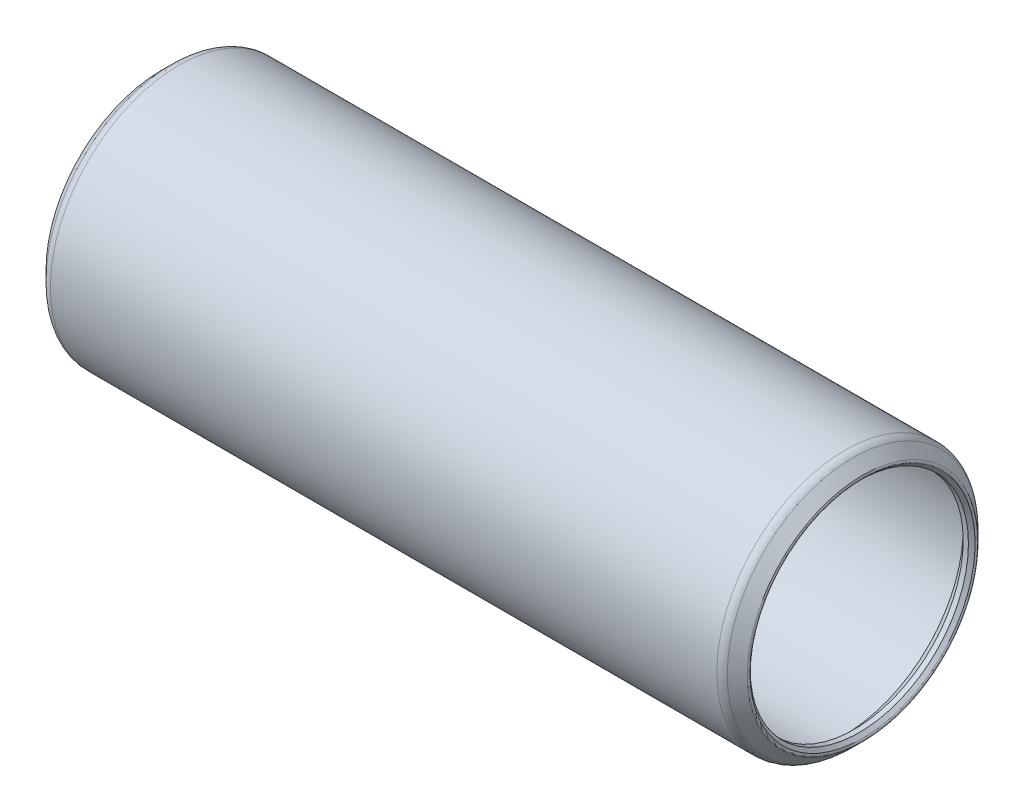
SolidWorks part; units mm, degrees
ref_plane "Front Plane" through (0, 0, 0) normal (0, 0, 1) x (1, 0, 0)
ref_plane "Top Plane" through (0, 0, 0) normal (0, 1, 0) x (1, 0, 0)
ref_plane "Right Plane" through (0, 0, 0) normal (1, 0, 0) x (0, 0, -1)
ref_plane "Plane1" through (41.6052, 0, 0) normal (1, 0, 0) x (0, 0, -1)
sketch "Sketch1" plane through (0, 0, 0) normal (0, 0, 1) x (1, 0, 0)
  line L0 (-0.518, 6.8362) -> (-0.3175, 6.6357)
  line L1 (-0.3175, 6.6357) -> (0, 6.6357)
  line L2 (0, 6.6357) -> (0.635, 7.2707)
  line L3 (0.635, 7.2707) -> (40.9702, 7.2707)
  line L4 (40.9702, 7.2707) -> (41.6052, 6.6357)
  line L5 (41.6052, 6.6357) -> (41.9227, 6.6357)
  line L6 (41.9227, 6.6357) -> (42.1232, 6.8362)
  line L7 (42.1232, 7.0158) -> (41.5145, 7.6245)
  line L8 (41.0655, 7.8105) -> (0.5398, 7.8105)
  line L9 (0.0907, 7.6245) -> (-0.518, 7.0158)
  line L10 (41.6052, 0) -> (0, 0) construction
  arc A0 (-0.518, 7.0158) -> (-0.518, 6.8362) centre (-0.4282, 6.926) ccw
  arc A1 (42.1232, 6.8362) -> (42.1232, 7.0158) centre (42.0334, 6.926) ccw
  arc A2 (41.5145, 7.6245) -> (41.0655, 7.8105) centre (41.0655, 7.1755) ccw
  arc A3 (0.5398, 7.8105) -> (0.0907, 7.6245) centre (0.5397, 7.1755) ccw
revolve "Revolve1" add sketch "Sketch1" angle 360 about L10 reverse direction yes
ref_plane "Plane2" through (20.8026, 0, 0) normal (1, 0, 0) x (0, 0, -1)
ref_plane "cp1 XY" through (20.8026, 0, 0) normal (1, 0, 0) x (0, 0, -1)
ref_plane "cp1 XZ" through (0, 7.8105, 0) normal (0, -1, 0) x (-1, 0, 0)
ref_plane "cp1 YZ" through (0, 0, 0) normal (0, 0, -1) x (-1, 0, 0)
ref_axis "cp1 X" through (20.8026, 7.8105, 80.9) along (0, 0, -1)
ref_axis "cp1 Y" through (20.8026, -50, 0) along (0, 1, 0)
ref_axis "cp1 Z" through (80.9, 7.8105, 0) along (-1, 0, 0)
sketch3d "cp1"
  point P0 (20.8026, 7.8105, 0)
ref_plane "cp2 XY" through (20.8026, 0, 0) normal (1, 0, 0) x (0, 0, -1)
ref_plane "cp2 XZ" through (0, 0, 0) normal (0, -1, 0) x (-1, 0, 0)
ref_plane "cp2 YZ" through (0, 0, -7.8105) normal (0, 0, -1) x (-1, 0, 0)
ref_axis "cp2 X" through (20.8026, 0, 80.9) along (0, 0, -1)
ref_axis "cp2 Y" through (20.8026, -50, -7.8105) along (0, 1, 0)
ref_axis "cp2 Z" through (80.9, 0, -7.8105) along (-1, 0, 0)
sketch3d "cp2"
  point P0 (20.8026, 0, -7.8105)
ref_plane "cp3 XY" through (20.8026, 0, 0) normal (1, 0, 0) x (0, 0, -1)
ref_plane "cp3 XZ" through (0, -7.8105, 0) normal (0, -1, 0) x (-1, 0, 0)
ref_plane "cp3 YZ" through (0, 0, 0) normal (0, 0, -1) x (-1, 0, 0)
ref_axis "cp3 X" through (20.8026, -7.8105, 80.9) along (0, 0, -1)
ref_axis "cp3 Y" through (20.8026, -50, 0) along (0, 1, 0)
ref_axis "cp3 Z" through (80.9, -7.8105, 0) along (-1, 0, 0)
sketch3d "cp3"
  point P0 (20.8026, -7.8105, 0)
ref_plane "cp4 XY" through (20.8026, 0, 0) normal (1, 0, 0) x (0, 0, -1)
ref_plane "cp4 XZ" through (0, 0, 0) normal (0, -1, 0) x (-1, 0, 0)
ref_plane "cp4 YZ" through (0, 0, 7.8105) normal (0, 0, -1) x (-1, 0, 0)
ref_axis "cp4 X" through (20.8026, 0, 80.9) along (0, 0, -1)
ref_axis "cp4 Y" through (20.8026, -50, 7.8105) along (0, 1, 0)
ref_axis "cp4 Z" through (80.9, 0, 7.8105) along (-1, 0, 0)
sketch3d "cp4"
  point P0 (20.8026, 0, 7.8105)
ref_plane "tube_front XY" through (0, 0, 0) normal (1, 0, 0) x (0, 0, -1)
ref_plane "tube_front XZ" through (0, 0, 0) normal (0, -1, 0) x (-1, 0, 0)
ref_plane "tube_front YZ" through (0, 0, 0) normal (0, 0, -1) x (-1, 0, 0)
ref_axis "tube_front X" through (0, 0, 80.9) along (0, 0, -1)
ref_axis "tube_front Y" through (0, -50, 0) along (0, 1, 0)
ref_axis "tube_front Z" through (80.9, 0, 0) along (-1, 0, 0)
sketch3d "tube_front"
  point P0 (0, 0, 0)
ref_plane "tube_rear XY" through (41.6052, 0, 0) normal (1, 0, 0) x (0, 0, -1)
ref_plane "tube_rear XZ" through (0, 0, 0) normal (0, -1, 0) x (-1, 0, 0)
ref_plane "tube_rear YZ" through (0, 0, 0) normal (0, 0, -1) x (-1, 0, 0)
ref_axis "tube_rear X" through (41.6052, 0, 80.9) along (0, 0, -1)
ref_axis "tube_rear Y" through (41.6052, -50, 0) along (0, 1, 0)
ref_axis "tube_rear Z" through (80.9, 0, 0) along (-1, 0, 0)
sketch3d "tube_rear"
  point P0 (41.6052, 0, 0)
